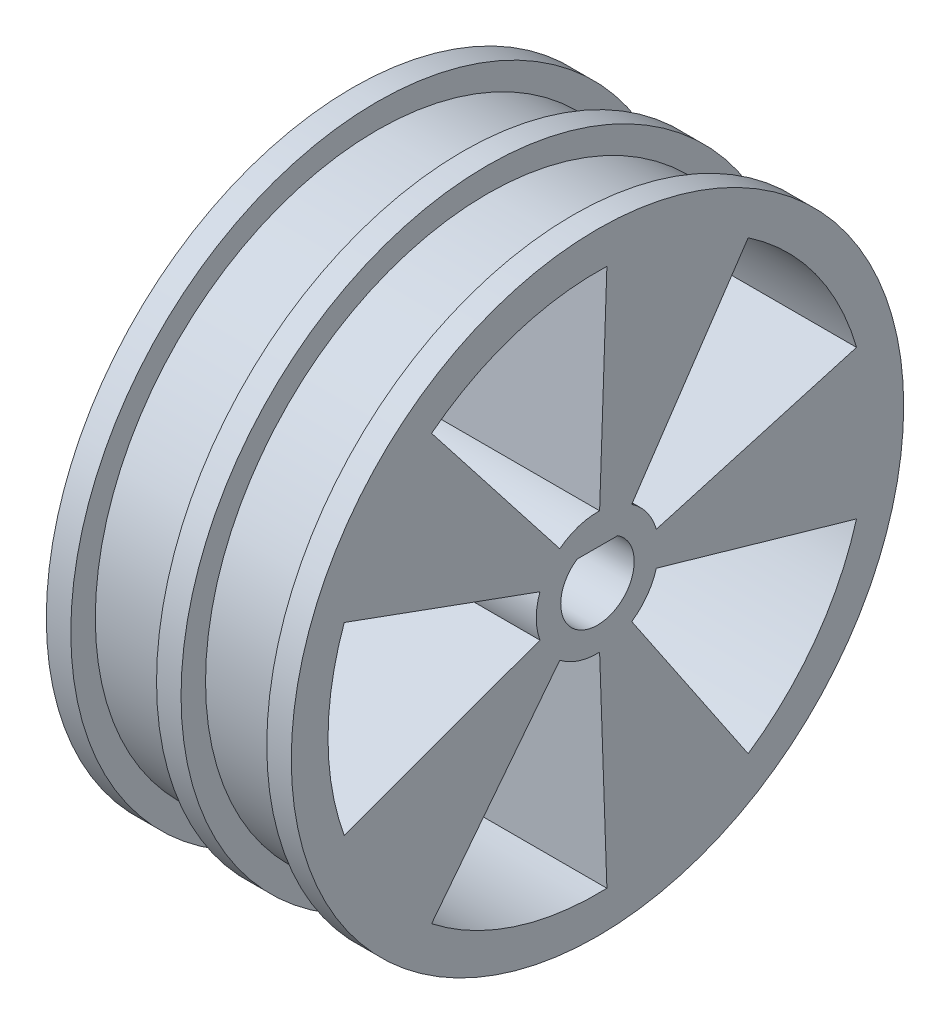
SolidWorks part; units mm, degrees
ref_plane "Plan de face" through (0, 0, 0) normal (0, 0, 1) x (1, 0, 0)
ref_plane "Plan de dessus" through (0, 0, 0) normal (0, 1, 0) x (1, 0, 0)
ref_plane "Plan de droite" through (0, 0, 0) normal (1, 0, 0) x (0, 0, -1)
sketch "Esquisse1" plane through (0, 0, 0) normal (1, 0, 0) x (0, 0, -1)
  line L0 (-1.6583, 2.5) -> (1.6583, 2.5)
  line L1 (0, 0) -> (0, 4.7784) construction
  arc A0 (-1.6583, 2.5) -> (1.6583, 2.5) centre (0, 0) ccw
  circle A1 centre (0, 0) radius 25
  point P6 (0, 3)
  dimension "D1" = 6
  dimension "D3" = 50
  dimension "D2" = 0.5
extrude "BASE" add sketch "Esquisse1" along normal blind 10 and the other way blind 10
ref_plane "PLAN GORGE" through (-8, 0, 0) normal (-1, 0, 0) x (0, 0, 1)
sketch "Esquisse2" plane through (-8, 0, 0) normal (-1, 0, 0) x (0, 0, 1)
  circle A0 centre (0, 0) radius 25
  circle A1 centre (0, 0) radius 23
  circle A5 centre (0, 0) radius 25 construction
  dimension "D1" = 2
extrude "VIDE GORGE" cut sketch "Esquisse2" against normal blind 7
mirror "SYM GORGE" about plane through (0, 0, 0) normal (1, 0, 0) of "VIDE GORGE"
sketch "Esquisse4" plane through (10, 0, 0) normal (1, 0, 0) x (0, 0, -1)
  line L0 (0, 0) -> (-22, 0) construction
  line L1 (-4.6985, 1.7101) -> (-20.6732, 7.5244)
  line L2 (-4.6985, -1.7101) -> (-20.6732, -7.5244)
  line L3 (0.1745, 4.997) -> (0.7678, 21.9866)
  line L4 (-3.0783, 3.9401) -> (-13.5446, 17.3362)
  line L5 (4.8063, 1.3782) -> (21.1478, 6.064)
  line L6 (2.796, 4.1452) -> (12.3022, 18.2388)
  line L7 (2.796, -4.1452) -> (12.3022, -18.2388)
  line L8 (4.8063, -1.3782) -> (21.1478, -6.064)
  line L9 (-3.0783, -3.9401) -> (-13.5446, -17.3362)
  line L10 (0.1745, -4.997) -> (0.7678, -21.9866)
  circle A0 centre (0, 0) radius 5
  arc A1 (-20.6732, 7.5244) -> (-20.6732, -7.5244) centre (0, 0) ccw
  circle A2 centre (0, 0) radius 25 construction
  arc A3 (0.7678, 21.9866) -> (-13.5446, 17.3362) centre (0, 0) ccw
  arc A4 (21.1478, 6.064) -> (12.3022, 18.2388) centre (0, 0) ccw
  arc A5 (12.3022, -18.2388) -> (21.1478, -6.064) centre (0, 0) ccw
  arc A6 (-13.5446, -17.3362) -> (0.7678, -21.9866) centre (0, 0) ccw
  point P30 (0, 0)
  dimension "D1" = 3
  dimension "D2" = 10
  dimension "D3" = 20
  dimension "D4" = 20
  dimension "D5" = 5
extrude "VIDE JANTE" cut sketch "Esquisse4" against normal up to surface (20 mm away) contours L0 A0 L1 A1 | A0 L0 A1 L2 | L3 A3 L4 A0 | L5 A4 L6 A0 | L7 A5 L8 A0 | L9 A6 L10 A0 region at (10, -2.6406, 14.9755) region at (10, 2.6406, 14.9755) region at (10, 14.2425, 4.6277) region at (10, -14.2425, 4.6277) region at (10, 8.8023, -12.1154) region at (10, -8.8023, -12.1154) up to face at (-10, -0.25, 0)
sketch "Esquisse6" plane through (-10, 0, 0) normal (-1, 0, 0) x (0, 0, 1)
  circle A0 centre (0, 0) radius 3
extrude "VIDE BLOC AXE" cut sketch "Esquisse6" against normal blind 4
